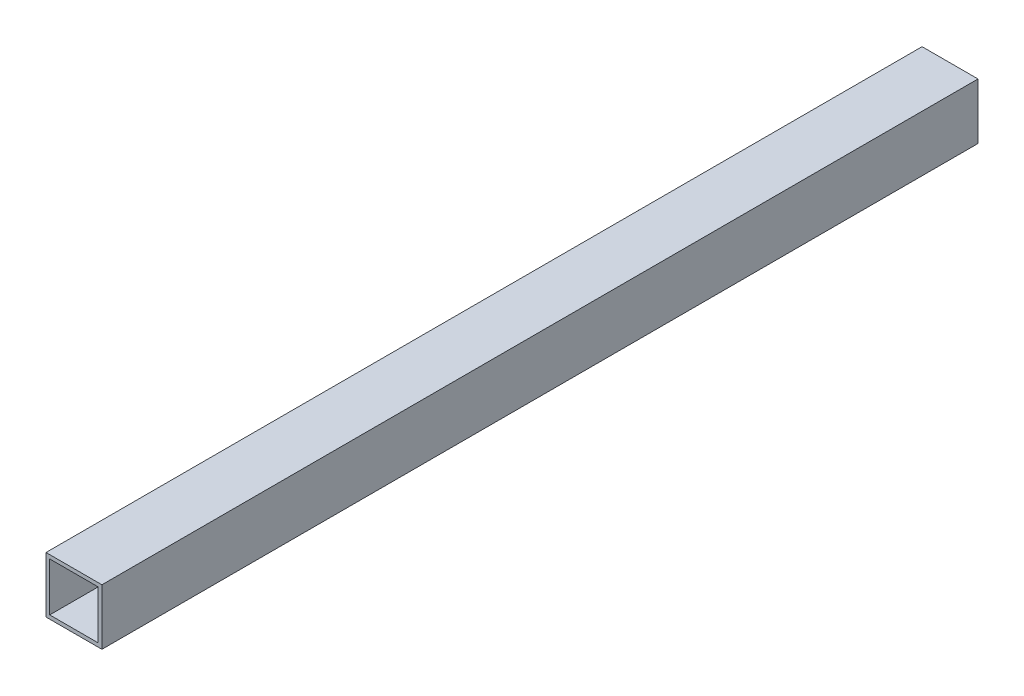
SolidWorks part; units mm, degrees
material "1060 合金"
ref_plane "前视基准面" through (0, 0, 0) normal (0, 0, 1) x (1, 0, 0)
ref_plane "上视基准面" through (0, 0, 0) normal (0, 1, 0) x (1, 0, 0)
ref_plane "右视基准面" through (0, 0, 0) normal (1, 0, 0) x (0, 0, -1)
other "Configuration Table"
sketch "草图1" plane through (0, 0, 0) normal (0, 0, 1) x (1, 0, 0)
  line L1 (0, 0) -> (15, 0)
  line L2 (0, 0) -> (0, -15)
  line L3 (0, -15) -> (15, -15)
  line L4 (15, 0) -> (15, -15)
  dimension "D1" = 15
  dimension "D2" = 15
extrude "拉伸-薄壁1" add sketch "草图1" along normal blind 235 thin thin type one direction reverse wall 1
sketch "草图2" plane through (0, -15, 0) normal (0, -1, 0) x (1, 0, 0)
  circle A1 centre (7.5, 825) radius 2.6
  circle A2 centre (7.5, 825) radius 2.6
  dimension "D1" = 0
extrude "切除-拉伸1" [suppressed] cut sketch "草图2" against normal up to next
